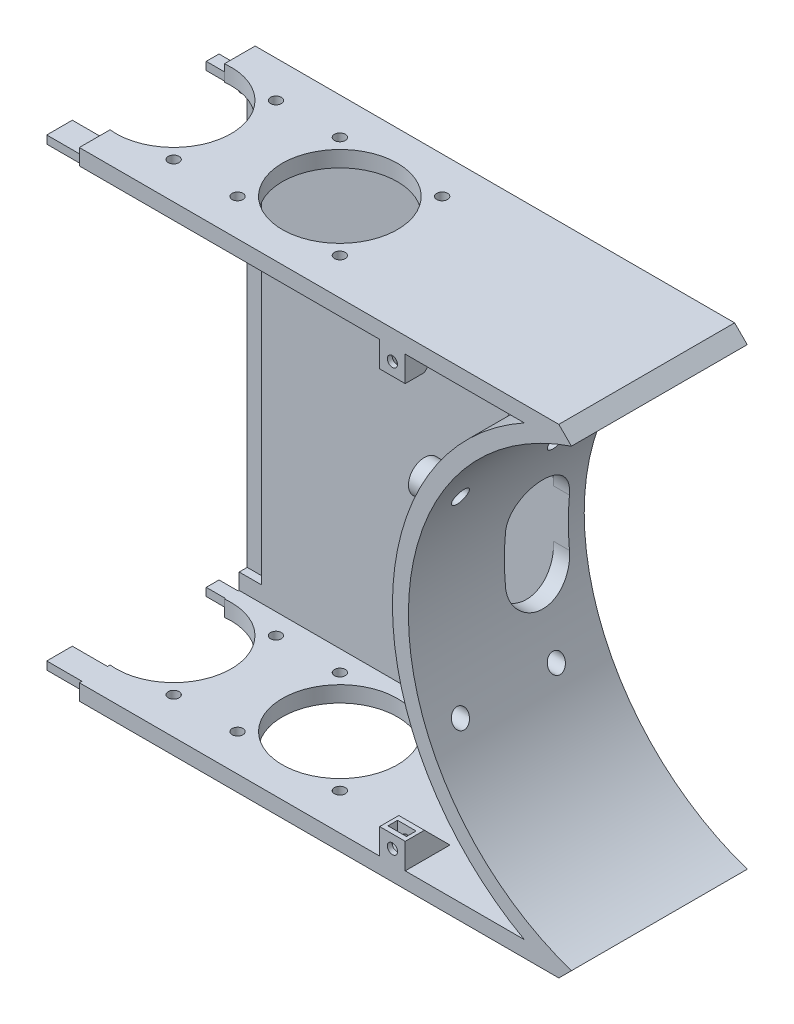
SolidWorks part; units mm, degrees
material "PLA"
ref_plane "Alzado" through (0, 0, 0) normal (0, 0, 1) x (1, 0, 0)
ref_plane "Planta" through (0, 0, 0) normal (0, 1, 0) x (1, 0, 0)
ref_plane "Vista lateral" through (0, 0, 0) normal (1, 0, 0) x (0, 0, -1)
sketch "Croquis1" plane through (0, 0, 0) normal (0, 0, 1) x (1, 0, 0)
  line L0 (-327.9437, 75) -> (-327.9437, -75)
  line L1 (-327.9437, 75) -> (-27.9437, 75)
  line L2 (-27.9437, 75) -> (-24, 71.0563)
  line L3 (-327.9437, -75) -> (-27.9437, -75)
  line L4 (-27.9437, -75) -> (-24, -71.0563)
  circle A0 centre (0, 0) radius 75 construction
  arc A1 (-24, 71.0563) -> (-24, -71.0563) centre (0, 0) ccw
  point P6 (-327.9437, 0)
  point P11 (-75, 0)
  dimension "D1" = 150
  dimension "D2" = 150
  dimension "D3" = 300
  dimension "D4" = 135
  dimension "D5" = 24
extrude "Saliente-Extruir1" add sketch "Croquis1" along normal blind 55
sketch "Croquis2" plane through (0, 0, 55) normal (0, 0, 1) x (1, 0, 0)
  line L2 (-27.9437, 70) -> (-327.9437, 70)
  line L3 (-38.7298, 70) -> (-322.9437, 70)
  line L5 (-322.9437, 75) -> (-322.9437, -75)
  line L6 (-322.9437, 70) -> (-322.9437, -70)
  line L8 (-327.9437, -70) -> (-27.9437, -70)
  line L9 (-322.9437, -70) -> (-38.7298, -70)
  arc A2 (-25.6, 75.7934) -> (-25.6, -75.7934) centre (0, 0) ccw
  arc A3 (-38.7298, 70) -> (-38.7298, -70) centre (0, 0) ccw
  dimension "D1" = 5
  dimension "D2" = 5
  dimension "D3" = 5
  dimension "D4" = 5
extrude "Cortar-Extruir1" cut sketch "Croquis2" against normal blind 50
sketch "Croquis3" plane through (0, 0, 0) normal (1, 0, 0) x (0, 0, -1)
  line L0 (-15, 7.5) -> (-15, -7.5) construction
  line L1 (-5, 7.5) -> (-5, -7.5)
  line L2 (-25, 7.5) -> (-25, -7.5)
  line L3 (-5, 70) -> (-5, -70) construction
  arc A0 (-5, 7.5) -> (-25, 7.5) centre (-15, 7.5) ccw
  arc A1 (-25, -7.5) -> (-5, -7.5) centre (-15, -7.5) ccw
  point P2 (-15, 0)
  dimension "D2" = 10
  dimension "D1" = 15
extrude "Cortar-Extruir2" cut sketch "Croquis3" against normal blind 82
sketch "Croquis4" plane through (0, 0, 0) normal (1, 0, 0) x (0, 0, -1)
  line L0 (-15, 30) -> (-15, -30) construction
  line L1 (-15, 30) -> (-45, 30) construction
  line L2 (-45, 30) -> (-45, -30) construction
  line L3 (-15, -30) -> (-45, -30) construction
  line L4 (-15, 30) -> (-45, -30) construction
  line L5 (-45, 30) -> (-15, -30) construction
  circle A0 centre (-45, -30) radius 2.6
  circle A1 centre (-15, -30) radius 2.6
  circle A2 centre (-15, 30) radius 2.6
  circle A3 centre (-45, 30) radius 2.6
  point P0 (-30, 0)
  dimension "D3" = 5.2
  dimension "D1" = 60
  dimension "D2" = 30
  dimension "D4" = 30
extrude "Cortar-Extruir3" cut sketch "Croquis4" against normal blind 82
ref_plane "Plano1" through (-80, 0, 0) normal (-1, 0, 0) x (0, 0, 1)
sketch "Croquis5" plane through (-80, 0, 0) normal (-1, 0, 0) x (0, 0, 1)
  circle A0 centre (45, -30) radius 2.6 construction
  circle A1 centre (15, -30) radius 2.6 construction
  circle A2 centre (45, 30) radius 2.6 construction
  circle A3 centre (15, 30) radius 2.6 construction
  circle A4 centre (45, -30) radius 2.6
  circle A5 centre (15, -30) radius 2.6
  circle A6 centre (45, 30) radius 2.6
  circle A7 centre (15, 30) radius 2.6
  circle A8 centre (45, 30) radius 5
  circle A9 centre (15, 30) radius 5
  circle A10 centre (45, -30) radius 5
  circle A11 centre (15, -30) radius 5
  dimension "D1" = 10
extrude "Saliente-Extruir2" add sketch "Croquis5" against normal up to surface (5.838 mm away) up to face at (-73.907, -30.6228, 47.5243)
sketch "Croquis6" plane through (0, 0, 5) normal (0, 0, 1) x (1, 0, 0)
  line L0 (-322.9437, 70) -> (-322.9437, -70) construction
  line L1 (-97.9437, -48) -> (-322.9437, -48) construction
  line L2 (-97.9437, -48) -> (-97.9437, 48) construction
  line L3 (-97.9437, 48) -> (-322.9437, 48) construction
  line L4 (-322.9437, -48) -> (-322.9437, 48) construction
  line L5 (-97.9437, -48) -> (-322.9437, 48) construction
  line L6 (-97.9437, 48) -> (-322.9437, -48) construction
  circle A0 centre (-302.9437, 44) radius 1.6
  circle A1 centre (-317.9437, -44) radius 1.6
  circle A2 centre (-190.9437, 43) radius 1.6
  circle A3 centre (-102.9437, 43) radius 1.6
  circle A4 centre (-102.9437, -43) radius 1.6
  point P0 (-210.4437, 0)
  dimension "D3" = 3.2
  dimension "D1" = 225
  dimension "D2" = 96
  dimension "D4" = 4
  dimension "D5" = 20
  dimension "D6" = 93
  dimension "D7" = 5
  dimension "D8" = 5
  dimension "D9" = 5
  dimension "D10" = 5
  dimension "D11" = 5
  dimension "D12" = 4
  dimension "D13" = 5
extrude "Cortar-Extruir4" cut sketch "Croquis6" against normal blind 82
sketch "Croquis7" plane through (-327.9437, 0, 0) normal (-1, 0, 0) x (0, 0, 1)
  line L0 (55, 75) -> (55, -75) construction
  line L1 (21.3, 43.8) -> (32.5, 43.8)
  line L2 (21.3, 43.8) -> (21.3, 34.3)
  line L3 (21.3, 34.3) -> (32.5, 34.3)
  line L4 (32.5, 43.8) -> (32.5, 34.3)
  line L5 (21.3, 43.8) -> (32.5, 34.3) construction
  line L6 (21.3, 34.3) -> (32.5, 43.8) construction
  line L7 (55, 75) -> (0, 75) construction
  point P0 (26.9, 39.05)
  dimension "D1" = 22.5
  dimension "D2" = 31.2
  dimension "D3" = 11.2
  dimension "D4" = 9.5
extrude "Cortar-Extruir5" cut sketch "Croquis7" against normal blind 13
sketch "Croquis8" plane through (-327.9437, 0, 0) normal (-1, 0, 0) x (0, 0, 1)
  line L0 (0, 75) -> (0, -75) construction
  line L1 (19.7, -8) -> (8.5, -8)
  line L2 (19.7, -8) -> (19.7, 4.4)
  line L3 (19.7, 4.4) -> (8.5, 4.4)
  line L4 (8.5, -8) -> (8.5, 4.4)
  line L5 (19.7, -8) -> (8.5, 4.4) construction
  line L6 (19.7, 4.4) -> (8.5, -8) construction
  line L7 (55, -75) -> (0, -75) construction
  point P0 (14.1, -1.8)
  point P9 (14.1, -8)
  dimension "D1" = 8.5
  dimension "D2" = 67
  dimension "D3" = 11.2
  dimension "D4" = 12.4
extrude "Cortar-Extruir6" cut sketch "Croquis8" against normal blind 13
sketch "Croquis9" plane through (0, 0, 5) normal (0, 0, 1) x (1, 0, 0)
  circle A0 centre (-302.9437, 44) radius 4
  circle A1 centre (-317.9437, -44) radius 4
  circle A2 centre (-190.9437, 43) radius 4
  circle A3 centre (-102.9437, 43) radius 4
  circle A4 centre (-102.9437, -43) radius 4
  circle A5 centre (-190.9437, 43) radius 1.6 construction
  circle A6 centre (-317.9437, -44) radius 1.6 construction
  circle A7 centre (-102.9437, 43) radius 1.6 construction
  circle A8 centre (-102.9437, -43) radius 1.6 construction
  circle A9 centre (-102.9437, -43) radius 1.6
  circle A10 centre (-102.9437, 43) radius 1.6
  circle A11 centre (-317.9437, -44) radius 1.6
  circle A12 centre (-190.9437, 43) radius 1.6
  circle A13 centre (-302.9437, 44) radius 1.6 construction
  circle A14 centre (-302.9437, 44) radius 1.6
  dimension "D1" = 8
extrude "Saliente-Extruir3" add sketch "Croquis9" along normal blind 14.8
sketch "Croquis10" plane through (0, -75, 0) normal (0, -1, 0) x (1, 0, 0)
  line L0 (-159.9437, 11.5) -> (-191.9437, 11.5) construction
  line L1 (-159.9437, 11.5) -> (-159.9437, 43.5) construction
  line L2 (-159.9437, 43.5) -> (-191.9437, 43.5) construction
  line L3 (-191.9437, 11.5) -> (-191.9437, 43.5) construction
  line L4 (-159.9437, 11.5) -> (-191.9437, 43.5) construction
  line L5 (-159.9437, 43.5) -> (-191.9437, 11.5) construction
  line L6 (-107.9437, 11.5) -> (-139.9437, 11.5) construction
  line L7 (-107.9437, 11.5) -> (-107.9437, 43.5) construction
  line L8 (-107.9437, 43.5) -> (-139.9437, 43.5) construction
  line L9 (-139.9437, 11.5) -> (-139.9437, 43.5) construction
  line L10 (-107.9437, 11.5) -> (-139.9437, 43.5) construction
  line L11 (-107.9437, 43.5) -> (-139.9437, 11.5) construction
  line L12 (-327.9437, 55) -> (-327.9437, 0) construction
  line L13 (-27.9437, 55) -> (-27.9437, 0) construction
  circle A0 centre (-191.9437, 43.5) radius 1.7
  circle A1 centre (-159.9437, 43.5) radius 1.7
  circle A2 centre (-191.9437, 11.5) radius 1.7
  circle A3 centre (-159.9437, 11.5) radius 1.7
  circle A4 centre (-139.9437, 43.5) radius 1.7
  circle A5 centre (-107.9437, 43.5) radius 1.7
  circle A6 centre (-139.9437, 11.5) radius 1.7
  circle A7 centre (-107.9437, 11.5) radius 1.7
  circle A12 centre (-175.9437, 27.5) radius 18
  circle A13 centre (-123.9437, 27.5) radius 18
  point P4 (-175.9437, 27.5)
  point P13 (-123.9437, 27.5)
  point P20 (-327.9437, 27.5)
  dimension "D3" = 3.4
  dimension "D6" = 3.4
  dimension "D9" = 36
  dimension "D1" = 32
  dimension "D2" = 32
  dimension "D4" = 32
  dimension "D5" = 32
  dimension "D7" = 20
  dimension "D8" = 80
extrude "Cortar-Extruir7" cut sketch "Croquis10" against normal blind 14.8
mirror "Simetría1" about plane through (0, 0, 0) normal (0, 1, 0) of "Cortar-Extruir7"
ref_plane "Plano2" through (0, 0, 13) normal (0, 0, 1) x (1, 0, 0)
sketch "Croquis11" plane through (0, 0, 13) normal (0, 0, 1) x (1, 0, 0)
  line L0 (-301.2687, 46.9012) -> (-296.5962, 46.9012)
  line L1 (-299.5937, 44) -> (-301.2687, 46.9012) construction
  line L2 (-301.2687, 46.9012) -> (-304.6187, 46.9012)
  line L3 (-304.6187, 46.9012) -> (-306.2937, 44)
  line L4 (-306.2937, 44) -> (-304.6187, 41.0988)
  line L5 (-304.6187, 41.0988) -> (-301.2687, 41.0988)
  line L6 (-301.2687, 41.0988) -> (-299.5937, 44) construction
  line L7 (-314.5937, -44) -> (-316.2687, -41.0988) construction
  line L8 (-316.2687, -41.0988) -> (-319.6187, -41.0988)
  line L9 (-319.6187, -41.0988) -> (-321.2937, -44)
  line L10 (-321.2937, -44) -> (-319.6187, -46.9012)
  line L11 (-319.6187, -46.9012) -> (-316.2687, -46.9012)
  line L12 (-316.2687, -46.9012) -> (-314.5937, -44) construction
  line L13 (-187.5937, 43) -> (-189.2687, 45.9012)
  line L14 (-189.2687, 45.9012) -> (-192.6187, 45.9012)
  line L15 (-192.6187, 45.9012) -> (-194.2937, 43) construction
  line L16 (-194.2937, 43) -> (-192.6187, 40.0988) construction
  line L17 (-192.6187, 40.0988) -> (-189.2687, 40.0988)
  line L18 (-189.2687, 40.0988) -> (-187.5937, 43)
  line L19 (-99.5937, 43) -> (-101.2687, 45.9012)
  line L20 (-101.2687, 45.9012) -> (-104.6187, 45.9012)
  line L21 (-104.6187, 45.9012) -> (-106.2937, 43) construction
  line L22 (-106.2937, 43) -> (-104.6187, 40.0988) construction
  line L23 (-104.6187, 40.0988) -> (-101.2687, 40.0988)
  line L24 (-101.2687, 40.0988) -> (-99.5937, 43)
  line L25 (-99.5937, -43) -> (-101.2687, -40.0988)
  line L26 (-101.2687, -40.0988) -> (-104.6187, -40.0988)
  line L27 (-104.6187, -40.0988) -> (-106.2937, -43) construction
  line L28 (-106.2937, -43) -> (-104.6187, -45.9012) construction
  line L29 (-104.6187, -45.9012) -> (-101.2687, -45.9012)
  line L30 (-101.2687, -45.9012) -> (-99.5937, -43)
  line L31 (-296.5962, 46.9012) -> (-296.5962, 41.0988)
  line L32 (-296.5962, 41.0988) -> (-301.2687, 41.0988)
  line L33 (-192.6187, 45.9012) -> (-196.6834, 45.9012)
  line L34 (-196.6834, 45.9012) -> (-196.6834, 40.0988)
  line L35 (-196.6834, 40.0988) -> (-192.6187, 40.0988)
  line L36 (-104.6187, 45.9012) -> (-110.7706, 45.9012)
  line L37 (-110.7706, 45.9012) -> (-110.7706, 40.0988)
  line L38 (-110.7706, 40.0988) -> (-104.6187, 40.0988)
  line L39 (-104.6187, -40.0988) -> (-109.0472, -40.0988)
  line L40 (-109.0472, -40.0988) -> (-109.1678, -45.9012)
  line L41 (-109.1678, -45.9012) -> (-104.6187, -45.9012)
  line L42 (-316.2687, -46.9012) -> (-310.7216, -46.9012)
  line L43 (-310.7216, -46.9012) -> (-310.7216, -41.0988)
  line L44 (-310.7216, -41.0988) -> (-316.2687, -41.0988)
  line L45 (-38.7298, 70) -> (-322.9437, 70) construction
  line L46 (-322.9437, -70) -> (-38.7298, -70) construction
  circle A0 centre (-302.9437, 44) radius 3.35 construction
  circle A1 centre (-317.9437, -44) radius 3.35 construction
  circle A2 centre (-190.9437, 43) radius 3.35 construction
  circle A3 centre (-102.9437, 43) radius 3.35 construction
  circle A4 centre (-102.9437, -43) radius 3.35 construction
  dimension "D1" = 6.7
extrude "Cortar-Extruir8" cut sketch "Croquis11" against normal blind 1.5 and the other way blind 1.5
sketch "Croquis12" plane through (0, 0, 0) normal (0, 1, 0) x (1, 0, 0)
  line L0 (-322.9437, -41) -> (-322.9437, -55)
  line L1 (-322.9437, -55) -> (-314.9437, -55)
  line L6 (-27.9437, -55) -> (-327.9437, -55) construction
  line L7 (-322.9437, -19.7) -> (-322.9437, -8.5) construction
  line L8 (-314.9437, -55) -> (-314.9437, -49)
  line L9 (-314.9437, -49) -> (-322.9437, -41)
  dimension "D1" = 8
  dimension "D2" = 45
  dimension "D3" = 6
extrude "Saliente-Extruir4" add sketch "Croquis12" along normal blind 4 and the other way blind 4
sketch "Croquis14" plane through (-80, 0, 0) normal (-1, 0, 0) x (0, 0, 1)
  line L0 (55, 70) -> (55, 62)
  line L1 (55, -70) -> (55, 70) construction
  line L3 (5, 70) -> (55, 70) construction
  line L4 (41, 70) -> (55, 70)
  line L5 (55, -70) -> (55, -62)
  line L7 (5, -70) -> (55, -70) construction
  line L8 (41, -70) -> (55, -70)
  line L9 (55, 62) -> (49, 62)
  line L10 (49, 62) -> (41, 70)
  line L11 (41, -70) -> (49, -62)
  line L12 (49, -62) -> (55, -62)
  dimension "D2" = 8
  dimension "D3" = 45
  dimension "D4" = 8
  dimension "D5" = 6
extrude "Saliente-Extruir5" add sketch "Croquis14" along normal blind 4 and the other way blind 4
sketch "Croquis13" plane through (0, 0, 55) normal (0, 0, 1) x (1, 0, 0)
  line L0 (-322.9437, 4) -> (-314.9437, -4) construction
  line L1 (-314.9437, 4) -> (-322.9437, -4) construction
  line L2 (-84, 70) -> (-76, 62) construction
  line L4 (-76, 70) -> (-84, 62) construction
  line L6 (-84, -62) -> (-76, -70) construction
  line L7 (-84, -70) -> (-76, -62) construction
  line L8 (-76, -70) -> (-76, -62) construction
  line L9 (-84, -70) -> (-84, -62) construction
  circle A0 centre (-318.9437, 0) radius 1.6
  circle A2 centre (-80, -66) radius 1.6
  circle A3 centre (-80, 66) radius 1.6
  dimension "D1" = 3.2
extrude "Cortar-Extruir9" cut sketch "Croquis13" against normal blind 14
ref_plane "Plano3" through (-160, 0, 0) normal (-1, 0, 0) x (0, 0, 1)
ref_plane "Plano4" through (0, 0, 52) normal (0, 0, 1) x (1, 0, 0)
mirror "Simetría2" about plane through (-160, 0, 0) normal (-1, 0, 0) of "Cortar-Extruir9", "Saliente-Extruir5"
sketch "Croquis17" plane through (0, 0, 52) normal (0, 0, 1) x (1, 0, 0)
  line L0 (-322.9437, 70) -> (-322.9437, 4) construction
  line L1 (-315.5937, 0) -> (-317.2687, 2.9012) construction
  line L2 (-317.2687, 2.9012) -> (-320.6187, 2.9012)
  line L3 (-320.6187, 2.9012) -> (-322.2937, 0)
  line L4 (-322.2937, 0) -> (-320.6187, -2.9012)
  line L5 (-320.6187, -2.9012) -> (-317.2687, -2.9012)
  line L6 (-317.2687, -2.9012) -> (-315.5937, 0) construction
  line L7 (-240, -62.65) -> (-242.9012, -64.325) construction
  line L8 (-242.9012, -64.325) -> (-242.9012, -67.675)
  line L9 (-242.9012, -67.675) -> (-240, -69.35)
  line L10 (-240, -69.35) -> (-237.0988, -67.675)
  line L11 (-237.0988, -67.675) -> (-237.0988, -64.325)
  line L12 (-237.0988, -64.325) -> (-240, -62.65) construction
  line L13 (-80, -62.65) -> (-82.9012, -64.325) construction
  line L14 (-82.9012, -64.325) -> (-82.9012, -67.675)
  line L15 (-82.9012, -67.675) -> (-80, -69.35)
  line L16 (-80, -69.35) -> (-77.0988, -67.675)
  line L17 (-77.0988, -67.675) -> (-77.0988, -64.325)
  line L18 (-77.0988, -64.325) -> (-80, -62.65) construction
  line L19 (-80, 62.65) -> (-77.0988, 64.325) construction
  line L20 (-77.0988, 64.325) -> (-77.0988, 67.675)
  line L21 (-77.0988, 67.675) -> (-80, 69.35)
  line L22 (-80, 69.35) -> (-82.9012, 67.675)
  line L23 (-82.9012, 67.675) -> (-82.9012, 64.325)
  line L24 (-82.9012, 64.325) -> (-80, 62.65) construction
  line L25 (-240, 62.65) -> (-237.0988, 64.325) construction
  line L26 (-237.0988, 64.325) -> (-237.0988, 67.675)
  line L27 (-237.0988, 67.675) -> (-240, 69.35)
  line L28 (-240, 69.35) -> (-242.9012, 67.675)
  line L29 (-242.9012, 67.675) -> (-242.9012, 64.325)
  line L30 (-242.9012, 64.325) -> (-240, 62.65) construction
  line L31 (-322.9437, -70) -> (-244, -70) construction
  line L32 (-317.2687, 2.9012) -> (-310.6187, 2.9012)
  line L33 (-310.6187, 2.9012) -> (-310.6187, -2.9012)
  line L34 (-310.6187, -2.9012) -> (-317.2687, -2.9012)
  line L35 (-242.9012, 64.325) -> (-242.9012, 57.675)
  line L36 (-242.9012, 57.675) -> (-237.0988, 57.675)
  line L37 (-237.0988, 57.675) -> (-237.0988, 64.325)
  line L38 (-82.9012, 64.325) -> (-82.9012, 57.675)
  line L39 (-82.9012, 57.675) -> (-76.8873, 57.675)
  line L40 (-76.8873, 57.675) -> (-77.0988, 64.325)
  line L41 (-82.9012, -64.325) -> (-82.9012, -57.675)
  line L42 (-82.9012, -57.675) -> (-77.0988, -57.675)
  line L43 (-77.0988, -57.675) -> (-77.0988, -64.325)
  line L44 (-242.9012, -64.325) -> (-242.9012, -57.675)
  line L45 (-242.9012, -57.675) -> (-237.0988, -57.675)
  line L46 (-237.0988, -57.675) -> (-237.0988, -64.325)
  circle A0 centre (-318.9437, 0) radius 3.35 construction
  circle A1 centre (-240, -66) radius 3.35 construction
  circle A2 centre (-80, -66) radius 3.35 construction
  circle A3 centre (-80, 66) radius 3.35 construction
  circle A4 centre (-240, 66) radius 3.35 construction
  dimension "D1" = 6.7
  dimension "D2" = 10
extrude "Cortar-Extruir10" cut sketch "Croquis17" against normal blind 1.5 and the other way blind 1.5
sketch "Croquis18" plane through (0, 0, 0) normal (0, 0, 1) x (1, 0, 0)
  line L0 (-327.9437, 75) -> (-327.9437, -75) construction
  line L1 (-177.9437, -100) -> (-337.9437, -100)
  line L2 (-177.9437, -100) -> (-177.9437, 100)
  line L3 (-177.9437, 100) -> (-337.9437, 100)
  line L4 (-337.9437, -100) -> (-337.9437, 100)
  line L5 (-177.9437, -100) -> (-337.9437, 100) construction
  line L6 (-177.9437, 100) -> (-337.9437, -100) construction
  line L7 (-322.9437, 70) -> (-322.9437, 4) construction
  point P0 (-257.9437, 0)
  dimension "D1" = 150
  dimension "D2" = 65
  dimension "D3" = 200
extrude "Cortar-Extruir11" cut sketch "Croquis18" along normal blind 122
sketch "Croquis19" plane through (0, -70, 0) normal (0, 1, 0) x (1, 0, 0)
  line L0 (-177.9437, -55) -> (-177.9437, -45.3885) construction
  line L1 (-166.9437, -46.1943) -> (-188.9437, -46.1943)
  line L2 (-166.9437, -46.1943) -> (-166.9437, -54.1943)
  line L3 (-166.9437, -54.1943) -> (-188.9437, -54.1943)
  line L4 (-188.9437, -46.1943) -> (-188.9437, -54.1943)
  line L5 (-166.9437, -46.1943) -> (-188.9437, -54.1943) construction
  line L6 (-166.9437, -54.1943) -> (-188.9437, -46.1943) construction
  line L7 (-177.9437, -9.6115) -> (-177.9437, -5) construction
  line L8 (-171.9437, -5.3057) -> (-183.9437, -5.3057)
  line L9 (-171.9437, -5.3057) -> (-171.9437, -9.3057)
  line L10 (-171.9437, -9.3057) -> (-183.9437, -9.3057)
  line L11 (-183.9437, -5.3057) -> (-183.9437, -9.3057)
  line L12 (-171.9437, -5.3057) -> (-183.9437, -9.3057) construction
  line L13 (-171.9437, -9.3057) -> (-183.9437, -5.3057) construction
  point P0 (-177.9437, -50.1943)
  point P7 (-177.9437, -7.3057)
  dimension "D1" = 8
  dimension "D2" = 4
  dimension "D3" = 12
  dimension "D4" = 22
extrude "Saliente-Extruir6" add sketch "Croquis19" against normal blind 2.5
mirror "Simetría3" about plane through (0, 0, 0) normal (0, 1, 0) of "Saliente-Extruir6"
sketch "Croquis21" plane through (0, 0, 5) normal (0, 0, 1) x (1, 0, 0)
  line L0 (-177.9437, 70) -> (-177.9437, -70) construction
  line L1 (-170.9437, -65) -> (-184.9437, -65)
  line L2 (-170.9437, -65) -> (-170.9437, 65)
  line L3 (-170.9437, 65) -> (-184.9437, 65)
  line L4 (-184.9437, -65) -> (-184.9437, 65)
  line L5 (-170.9437, -65) -> (-184.9437, 65) construction
  line L6 (-170.9437, 65) -> (-184.9437, -65) construction
  point P0 (-177.9437, 0)
  dimension "D1" = 130
  dimension "D2" = 14
extrude "Cortar-Extruir12" cut sketch "Croquis21" against normal blind 2.5
